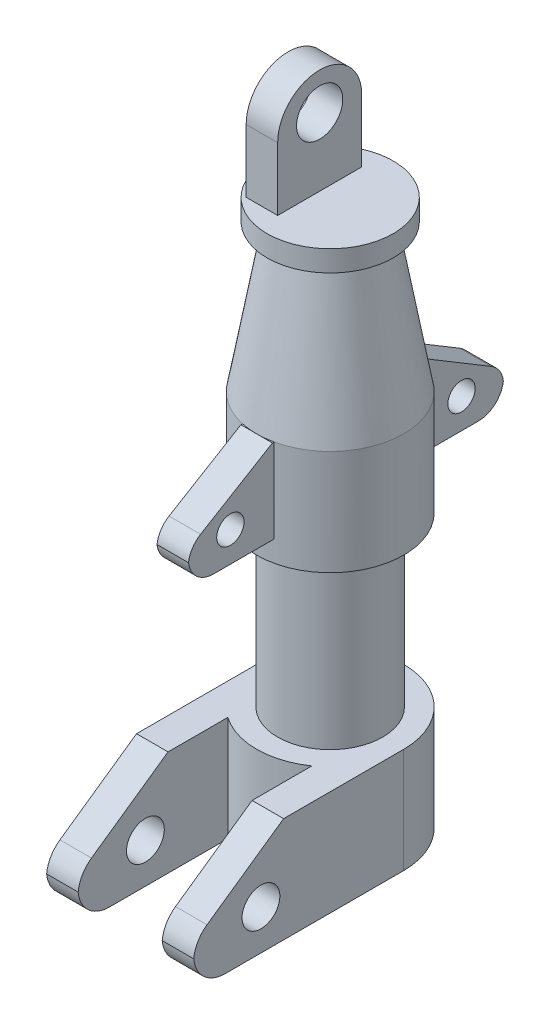
SolidWorks part; units mm, degrees
ref_plane "Front Plane" through (0, 0, 0) normal (0, 0, 1) x (1, 0, 0)
ref_plane "Top Plane" through (0, 0, 0) normal (0, 1, 0) x (1, 0, 0)
ref_plane "Right Plane" through (0, 0, 0) normal (1, 0, 0) x (0, 0, -1)
sketch "Sketch1" plane through (0, 0, 0) normal (0, 1, 0) x (1, 0, 0)
  circle A0 centre (0, 0) radius 35
  dimension "D1" = 70
ref_plane "Plane1" through (0, 50, 0) normal (0, 1, 0) x (1, 0, 0)
ref_plane "Plane2" through (0, 130, 0) normal (0, 1, 0) x (1, 0, 0)
ref_plane "Plane3" through (0, 180, 0) normal (0, 1, 0) x (1, 0, 0)
ref_plane "Plane4" through (0, 250, 0) normal (0, 1, 0) x (1, 0, 0)
extrude "Boss-Extrude1" add sketch "Sketch1" along normal blind 50 contours A0
sketch "Sketch6" plane through (0, 50, 0) normal (0, 1, 0) x (1, 0, 0)
  circle A0 centre (0, 0) radius 25
  dimension "D1" = 50
extrude "Boss-Extrude2" add sketch "Sketch6" along normal blind 80
sketch "Sketch7" plane through (0, 130, 0) normal (0, 1, 0) x (1, 0, 0)
  circle A0 centre (0, 0) radius 35
  dimension "D1" = 70
extrude "Boss-Extrude3" add sketch "Sketch7" along normal blind 50
ref_plane "Plane6" through (0, 250, 0) normal (0, 1, 0) x (1, 0, 0)
sketch "Sketch10" plane through (0, 250, 0) normal (0, 1, 0) x (1, 0, 0)
  circle A0 centre (0, 0) radius 30
  dimension "D1" = 60
extrude "Boss-Extrude5" add sketch "Sketch10" along normal blind 10 separate body
sketch "Sketch11" plane through (0, 0, 0) normal (1, 0, 0) x (0, 0, -1)
  line L0 (0, 250) -> (22.6571, 250)
  line L1 (-30, 250) -> (30, 250) construction
  line L2 (22.6571, 250) -> (35, 180)
  line L3 (35, 180) -> (0, 180)
  line L4 (35, 180) -> (-35, 180) construction
  line L5 (0, 180) -> (0, 250)
  dimension "D1" = 10
revolve "Revolve1" add sketch "Sketch11" angle 360 about L5
sketch "Sketch12" plane through (0, 0, 0) normal (0, -1, 0) x (1, 0, 0)
  line L0 (-35, 0) -> (-35, 100.0092)
  line L1 (-35, 100.0092) -> (35, 100.0092)
  line L2 (35, 100.0092) -> (35, 0)
  line L3 (35, 0) -> (-35, 0)
  circle A0 centre (0, 0) radius 35 construction
extrude "Boss-Extrude6" add sketch "Sketch12" against normal blind 50
sketch "Sketch13" plane through (-35, 0, 0) normal (-1, 0, 0) x (0, 0, 1)
  line L0 (57.1647, 50) -> (100.0092, 20)
  line L1 (100.0092, 50) -> (0, 50) construction
  line L2 (100.0092, 50) -> (100.0092, 0) construction
  line L4 (100.0092, 0) -> (0, 0) construction
  line L5 (57.1647, 50) -> (100.0092, 50)
  line L6 (100.0092, 50) -> (100.0092, 20)
  dimension "D1" = 35
  dimension "D2" = 20
extrude "Cut-Extrude1" cut sketch "Sketch13" against normal through all
sketch "Sketch14" plane through (0, 0, 0) normal (0, -1, 0) x (1, 0, 0)
  line L0 (-35, 100.0092) -> (-35, 0) construction
  line L1 (-20, 108.7406) -> (20, 108.7406)
  line L2 (-20, 108.7406) -> (-20, 28.7228)
  line L4 (20, 108.7406) -> (20, 28.7228)
  line L5 (35, 0) -> (35, 100.0092) construction
  arc A0 (20, 28.7228) -> (-20, 28.7228) centre (0, 0) ccw
  dimension "D1" = 70
  dimension "D2" = 15
  dimension "D3" = 15
extrude "Cut-Extrude2" cut sketch "Sketch14" against normal through all
fillet "Fillet1" radius 15 4 edges at (27.5, 0, 100.0092) (27.5, 20, 100.0092) (-27.5, 0, 100.0092) (-27.5, 20, 100.0092)
sketch "Sketch15" plane through (-35, 0, 0) normal (-1, 0, 0) x (0, 0, 1)
  line L0 (85.0092, 0) -> (0, 0) construction
  circle A0 centre (67.9433, 19) radius 9
  dimension "D1" = 18
  dimension "D2" = 19
  dimension "D3" = 32
extrude "Cut-Extrude3" cut sketch "Sketch15" against normal through all
sketch "Sketch16" plane through (0, 0, 0) normal (1, 0, 0) x (0, 0, -1)
  line L0 (-35, 180) -> (-75, 155.9656)
  line L1 (-75, 155.9656) -> (-75, 140)
  line L2 (-75, 140) -> (-35, 140)
  line L3 (-35, 180) -> (-35, 130) construction
  line L5 (-35, 130) -> (35, 130) construction
  line L6 (-35, 180) -> (0, 180)
  line L7 (-35, 180) -> (35, 180) construction
  line L8 (0, 180) -> (0, 140)
  line L9 (0, 140) -> (-35, 140)
  dimension "D3" = 31
  dimension "D1" = 10
  dimension "D2" = 75
extrude "Boss-Extrude8" add sketch "Sketch16" along normal blind 7.5 and the other way blind 7.5 contours L0 L1 L2 L9 L8 L6
fillet "Fillet2" radius 12 2 edges at (0, 140, 75) (0, 155.9656, 75)
sketch "Sketch17" plane through (7.5, 0, 0) normal (1, 0, 0) x (0, 0, -1)
  line L0 (-34.187, 140) -> (-63, 140) construction
  circle A0 centre (-55, 154.29) radius 6.5
  dimension "D1" = 13
  dimension "D2" = 14.29
  dimension "D3" = 55
extrude "Cut-Extrude4" cut sketch "Sketch17" against normal through all
mirror "Mirror1" about plane through (0, 0, 0) normal (0, 0, 1) of "Boss-Extrude8"
fillet "Fillet3" radius 12 2 edges at (0, 140, -75) (0, 155.9656, -75)
mirror "Mirror2" about plane through (0, 0, 0) normal (0, 0, 1) of "Cut-Extrude4"
sketch "Sketch18" plane through (0, 260, 0) normal (0, 1, 0) x (1, 0, 0)
  line L1 (-20, 20) -> (-5, 20)
  line L2 (-20, 20) -> (-20, -20)
  line L3 (-20, -20) -> (-5, -20)
  line L4 (-5, 20) -> (-5, -20)
  dimension "D1" = 15
  dimension "D2" = 5
  dimension "D3" = 40
  dimension "D4" = 20
extrude "Boss-Extrude9" add sketch "Sketch18" along normal blind 50
sketch "Sketch19" plane through (-20, 0, 0) normal (-1, 0, 0) x (0, 0, 1)
  line L0 (-20, 310) -> (20, 310) construction
  line L1 (-20, 290) -> (-20, 310)
  line L2 (-20, 310) -> (20, 310)
  line L3 (20, 310) -> (20, 290)
  arc A0 (20, 290) -> (-20, 290) centre (0, 290) ccw
  point P1 (0, 0)
  line M5 (20, 260) -> (20, 310)
  line M6 (20, 310) -> (-20, 310)
  line M7 (-20, 310) -> (-20, 260)
  dimension "D1" = 40
extrude "Cut-Extrude5" cut sketch "Sketch19" against normal through all contours A0 M5 M6 | A0 L2 M7 region at (-20, 305.5326, 15.5326) region at (-20, 305.5326, -15.5326)
sketch "Sketch20" plane through (-20, 0, 0) normal (-1, 0, 0) x (0, 0, 1)
  circle A0 centre (0, 292.4488) radius 11
  dimension "D1" = 22
extrude "Cut-Extrude6" cut sketch "Sketch20" against normal through all
